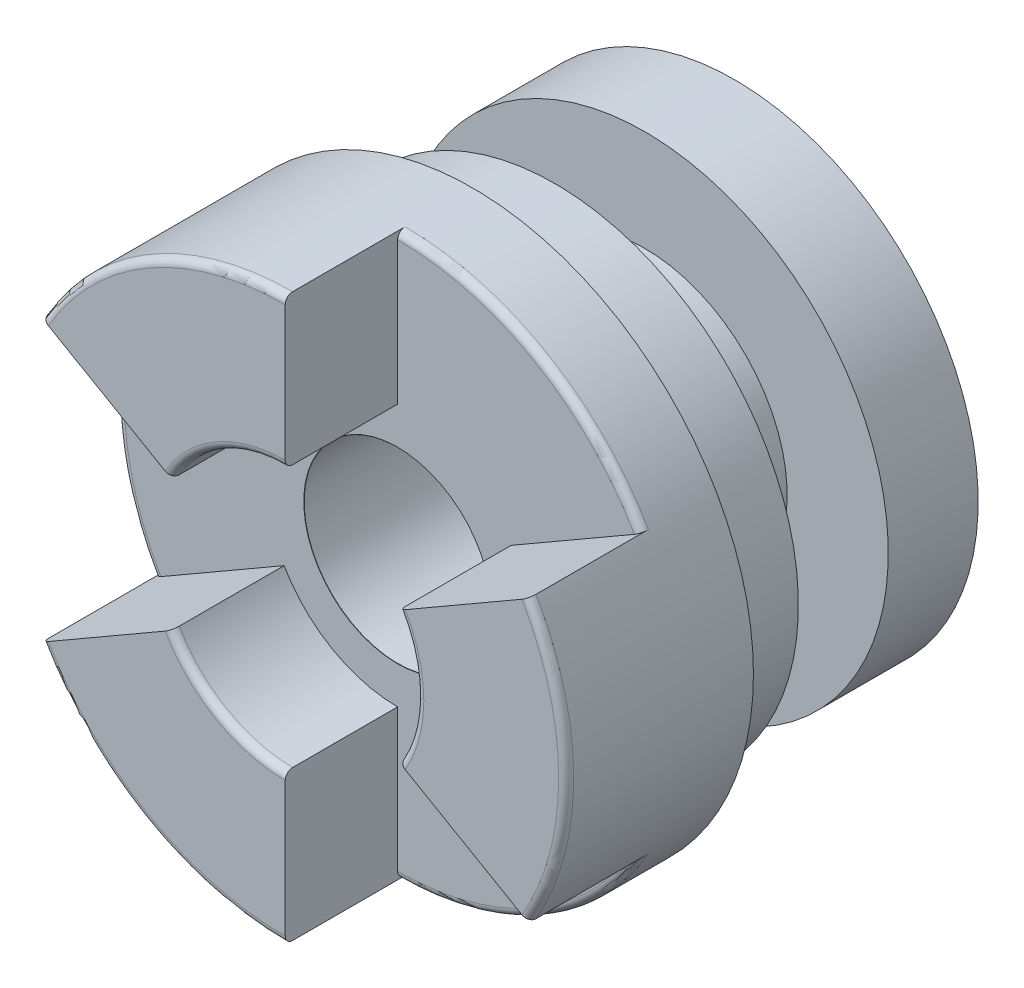
SolidWorks part; units mm, degrees
ref_plane "Front Plane" through (0, 0, 0) normal (0, 0, 1) x (1, 0, 0)
ref_plane "Top Plane" through (0, 0, 0) normal (0, 1, 0) x (1, 0, 0)
ref_plane "Right Plane" through (0, 0, 0) normal (1, 0, 0) x (0, 0, -1)
sketch "Sketch1" plane through (0, 0, 0) normal (0, 0, 1) x (1, 0, 0)
  line L0 (0, 0) -> (0, 29286.1864) construction
  line L1 (0, 0) -> (29286.1864, 0) construction
  circle A0 centre (0, 0) radius 37.5
  dimension "D1" = 75
extrude "Boss-Extrude1" add sketch "Sketch1" along normal blind 10
sketch "Sketch2" plane through (0, 0, 0) normal (0, 0, -1) x (-1, 0, 0)
  circle A0 centre (0, 0) radius 32.5
  dimension "D1" = 65
extrude "Boss-Extrude2" add sketch "Sketch2" along normal blind 11
sketch "Sketch3" plane through (0, 0, -11) normal (0, 0, -1) x (-1, 0, 0)
  circle A0 centre (0, 0) radius 19
  dimension "D1" = 38
extrude "Boss-Extrude3" add sketch "Sketch3" along normal blind 12
sketch "Sketch4" plane through (0, 0, -23) normal (0, 0, -1) x (-1, 0, 0)
  circle A0 centre (0, 0) radius 32.5 construction
  circle A1 centre (0, 0) radius 32.5
extrude "Boss-Extrude4" add sketch "Sketch4" along normal blind 12
sketch "Sketch5" plane through (0, 0, 10) normal (0, 0, 1) x (1, 0, 0)
  line L0 (0, 0) -> (0, 50000) construction
  line L1 (0, 0) -> (50000, 0) construction
  line L2 (0, 37.5) -> (0, 17.5)
  line L3 (0, 17.5) -> (0, 0) construction
  line L4 (-15.1554, 8.75) -> (-32.476, 18.75)
  line L5 (-15.1554, 8.75) -> (0, 0) construction
  line L6 (15.1554, 8.75) -> (32.476, 18.75)
  line L7 (32.476, -18.75) -> (15.1554, -8.75)
  line L8 (0, -17.5) -> (0, -37.5)
  line L9 (-32.476, -18.75) -> (-15.1554, -8.75)
  circle A0 centre (0, 0) radius 17.5
  circle A1 centre (0, 0) radius 37.5 construction
  circle A2 centre (0, 0) radius 37.5
  point P24 (0, 0)
  circle M8 centre (0, 0) radius 37.5
  dimension "D1" = 35
  dimension "D2" = 60
  dimension "D3" = 3
extrude "Boss-Extrude5" add sketch "Sketch5" along normal blind 15 contours A0 L2 L4 M8 | A0 L9 L8 M8 | A0 L7 L6 M8 region at (-13.709, 23.7447, 10) region at (27.4181, 0, 10) region at (-13.709, -23.7447, 10)
fillet "Fillet1" radius 1 9 edges at (37.5, 0, 25) (17.5, 0, 25) (-18.75, 32.476, 25) (-8.75, 15.1554, 25) (-8.75, -15.1554, 25) (-18.75, -32.476, 25) (-37.5, 0, 10) (18.75, -32.476, 10) (18.75, 32.476, 10)
hole_wizard "Ø25.0mm Dowel Hole1" positions "Sketch6" profile "Sketch7" hole size "Ø25.0" standard "ISO" end condition through all
sketch "Sketch6" plane through (0, 0, 10) normal (0, 0, 1) x (1, 0, 0)
  point P0 (0, 0)
sketch "Sketch7" plane through (0, 0, 10) normal (1, 0, 0) x (0, -1, 0)
  line L0 (0, 0) -> (0, 45)
  line L1 (0, 45) -> (12.5, 45)
  line L2 (12.5, 45) -> (12.5, 0.025)
  line L3 (12.5, 0.025) -> (12.525, 0)
  line L5 (12.525, 0) -> (0, 0)
  line L6 (-12.5, 0.025) -> (-12.525, 0) construction
  line L11 (0, -6.35) -> (0, 107.95) construction
  dimension "Thru Hole Dia." = 25
  dimension "Thru Hole Depth" = 45
  dimension "Near C'Sink Dia." = 25.05
  dimension "Near C'Sink Angle" = 90
sketch "Sketch9" plane through (0, 0, 0) normal (0, 1, 0) x (1, 0, 0)
  line L0 (0, -9.975) -> (15.8, -9.975)
  line L1 (12.5, -9.975) -> (-12.5, -9.975) construction
  line L2 (15.8, -9.975) -> (15.8, 35)
  line L3 (15.8, 35) -> (0, 35)
  line L4 (12.5, 35) -> (-12.5, 35) construction
  line L5 (0, 35) -> (0, -9.975)
  dimension "D1" = 15.8
  dimension "D2" = 15.8
extrude "Cut-Extrude2" cut sketch "Sketch9" against normal mid plane 8.5
sketch "Sketch12" plane through (0, 0, 9.975) normal (0, 0, -1) x (-1, 0, 0)
  line L3 (-11.7553, 4.25) -> (-15.8, 4.25)
  line L4 (-15.8, 4.25) -> (-15.8, -4.25)
  line L5 (-15.8, -4.25) -> (-11.7553, -4.25)
  line L6 (-11.7553, 4.25) -> (-15.8, 4.25)
  line L7 (-15.8, 4.25) -> (-15.8, -4.25)
  line L8 (-15.8, -4.25) -> (-11.7553, -4.25)
  arc A1 (-11.7553, 4.25) -> (-11.7553, -4.25) centre (0, 0) ccw
  arc A2 (-11.7553, 4.25) -> (-11.7553, -4.25) centre (0, 0) ccw
  dimension "D1" = 0
extrude "Cut-Extrude3" cut sketch "Sketch12" against normal mid plane 8.5
